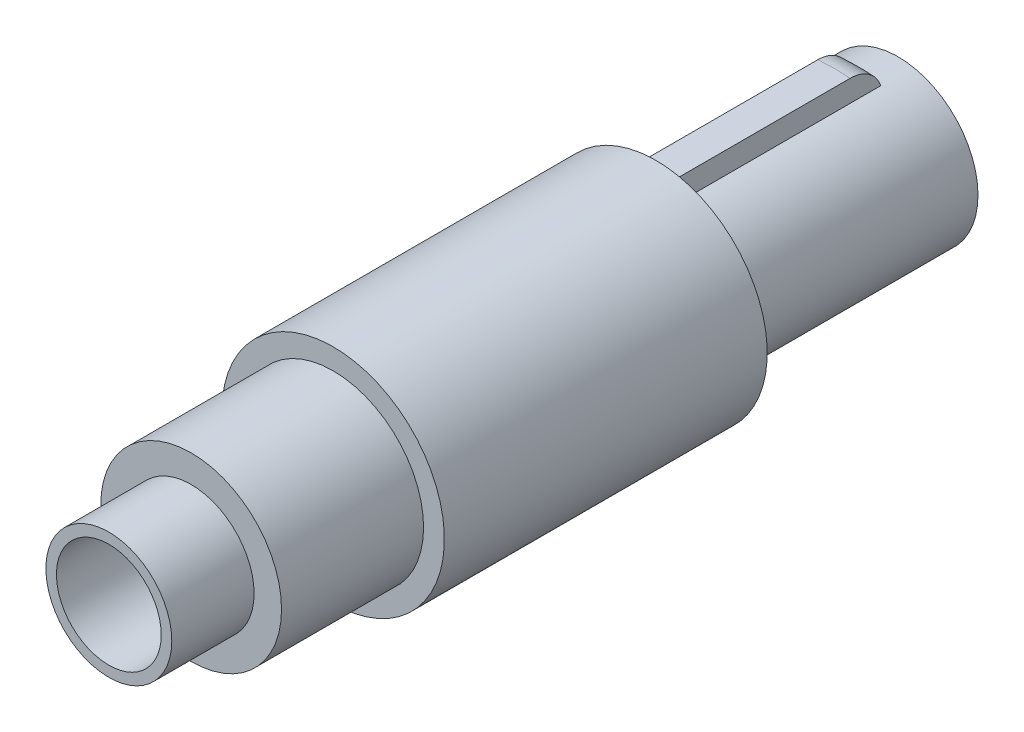
SolidWorks part; units mm, degrees
ref_plane "Front Plane" through (0, 0, 0) normal (0, 0, 1) x (1, 0, 0)
ref_plane "Top Plane" through (0, 0, 0) normal (0, 1, 0) x (1, 0, 0)
ref_plane "Right Plane" through (0, 0, 0) normal (1, 0, 0) x (0, 0, -1)
sketch "Sketch1" plane through (0, 0, 0) normal (0, 0, 1) x (1, 0, 0)
  circle A0 centre (0, 0) radius 6.89
extrude "Boss-Extrude1" add sketch "Sketch1" along normal blind 20
sketch "Sketch5" plane through (0, 0, 0) normal (0, 0, 1) x (1, 0, 0)
  circle A0 centre (0, 0) radius 4.95
extrude "Boss-Extrude3" add sketch "Sketch5" against normal blind 15
sketch "Sketch6" plane through (0, 0, 0) normal (0, 0, 1) x (1, 0, 0)
  circle A0 centre (0, 0) radius 5.6
  dimension "D1" = 11.2
extrude "Boss-Extrude4" add sketch "Sketch6" along normal blind 28.8
sketch "Sketch7" plane through (0, 0, 0) normal (0, 0, 1) x (1, 0, 0)
  circle A0 centre (0, 0) radius 3.9
  dimension "D1" = 7.8
extrude "Boss-Extrude5" add sketch "Sketch7" along normal blind 33.9
sketch "Sketch8" plane through (0, 0, 0) normal (0, 0, 1) x (1, 0, 0)
  circle A0 centre (0, 0) radius 3.245
extrude "Cut-Extrude1" cut sketch "Sketch8" against normal through all and the other way through all
sketch "Sketch9" plane through (0, 0, 0) normal (0, 0, 1) x (1, 0, 0)
  line L1 (-1.0718, 4.2064) -> (0.9282, 4.2064)
  line L2 (-1.0718, 4.2064) -> (-1.0718, 6.2064)
  line L3 (-1.0718, 6.2064) -> (0.9282, 6.2064)
  line L4 (0.9282, 4.2064) -> (0.9282, 6.2064)
  circle A0 centre (0, 0) radius 4.95 construction
  point P0 (0, 4.95)
extrude "Boss-Extrude8" add sketch "Sketch9" against normal blind 13
fillet "Fillet2" radius 2 1 edges at (-0.0718, 6.2064, -13)
